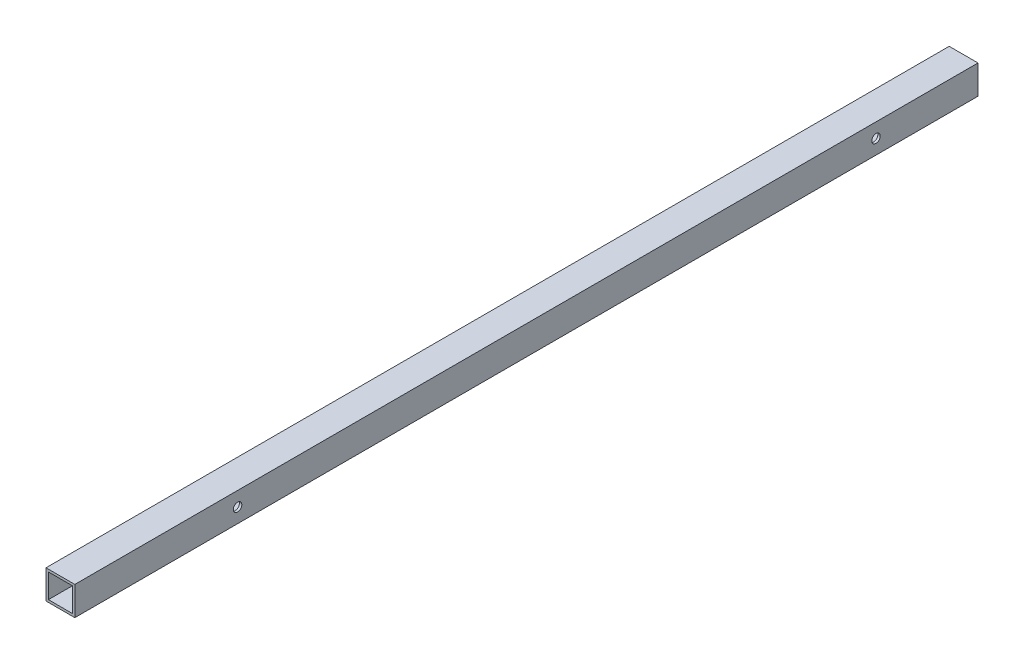
SolidWorks part; units mm, degrees
material "6061 Alloy"
ref_plane "Front Plane" through (0, 0, 0) normal (0, 0, 1) x (1, 0, 0)
ref_plane "Top Plane" through (0, 0, 0) normal (0, 1, 0) x (1, 0, 0)
ref_plane "Right Plane" through (0, 0, 0) normal (1, 0, 0) x (0, 0, -1)
sketch "Sketch1" plane through (0, 0, 0) normal (0, 0, 1) x (1, 0, 0)
  line L0 (19.05, 0) -> (15.875, 0) construction
  line L1 (-19.05, 0) -> (19.05, 0) construction
  line L2 (0, 19.05) -> (0, -19.05)
  point P7 (0, 0)
sketch "Sketch2" plane through (0, 0, 0) normal (1, 0, 0) x (0, 0, -1)
  line L0 (596.9, 0) -> (-596.9, 0)
  point P4 (0, 0)
  dimension "Length" = 1193.8
sketch "Sketch3" plane through (0, 0, 0) normal (0, 0, 1) x (1, 0, 0)
  line L0 (-19.05, 0) -> (19.05, 0) construction
  line L5 (19.05, -19.05) -> (-19.05, -19.05)
  line L6 (19.05, -19.05) -> (19.05, 19.05)
  line L11 (19.05, 19.05) -> (-19.05, 19.05)
  line L12 (-19.05, -19.05) -> (-19.05, 19.05)
  line L14 (19.05, -19.05) -> (-19.05, 19.05) construction
  line L15 (19.05, 19.05) -> (-19.05, -19.05) construction
  line L16 (15.875, -15.875) -> (-15.875, -15.875)
  line L17 (15.875, -15.875) -> (15.875, 15.875)
  line L18 (15.875, 15.875) -> (-15.875, 15.875)
  line L19 (-15.875, -15.875) -> (-15.875, 15.875)
  line L20 (15.875, -15.875) -> (-15.875, 15.875) construction
  line L21 (15.875, 15.875) -> (-15.875, -15.875) construction
  point P0 (0, 0)
  point P5 (0, 0)
  point P13 (15.875, -19.05)
  dimension "D1" = 3.175
  dimension "D3" = 38.1
  dimension "D4" = 38.1
  dimension "D2" = 3.175
extrude "Boss-Extrude1" add sketch "Sketch3" along normal up to vertex (596.9 mm away) and the other way up to vertex (596.9 mm away) up to point (0, 0, 596.9) other way up to point (0, 0, -596.9)
sketch "Sketch5" plane through (0, 0, 0) normal (1, 0, 0) x (0, 0, -1)
  line L0 (-596.9, 0) -> (596.9, 0) construction
  line L3 (-596.9, -19.05) -> (-596.9, 19.05) construction
  line L4 (596.9, -19.05) -> (596.9, 19.05) construction
  point P6 (-554.0375, 0)
  point P7 (-539.75, 0)
  point P8 (539.75, 0)
  point P10 (554.0375, 0)
  dimension "D1" = 42.8625
  dimension "D2" = 57.15
  dimension "D3" = 42.8625
  dimension "D4" = 57.15
sketch "Sketch9" plane through (19.05, 0, 0) normal (1, 0, 0) x (0, 0, -1)
  circle A0 centre (-381.772, 0) radius 5.6134
extrude "Cut-Extrude2" cut sketch "Sketch9" against normal through all
sketch "Sketch10" plane through (19.05, 0, 0) normal (1, 0, 0) x (0, 0, -1)
  circle A0 centre (462.0894, 0) radius 5.6134
extrude "Cut-Extrude3" cut sketch "Sketch10" against normal through all
equation "\"D1@Sketch3\"=\"Wall thickness@Sketch1\""
equation "\"D1@Sketch5\"=\"Width@Sketch1\"*1.125"
equation "\"D2@Sketch5\"=\"Width@Sketch1\"*1.5"
equation "\"D3@Sketch5\"=\"D1@Sketch5\""
equation "\"D4@Sketch5\"=\"D2@Sketch5\""
equation "\"D2@Sketch3\"=\"Wall Thickness@Sketch1\""
